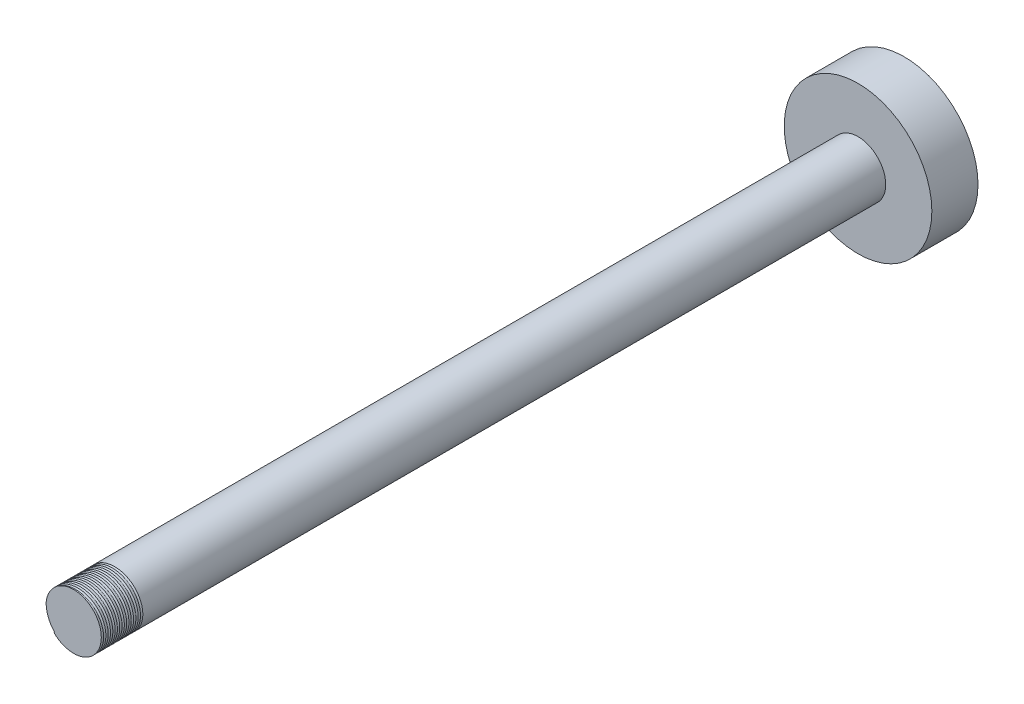
SolidWorks part; units mm, degrees
ref_plane "Front Plane" through (0, 0, 0) normal (0, 0, 1) x (1, 0, 0)
ref_plane "Top Plane" through (0, 0, 0) normal (0, 1, 0) x (1, 0, 0)
ref_plane "Right Plane" through (0, 0, 0) normal (1, 0, 0) x (0, 0, -1)
sketch "Sketch1" plane through (0, 0, 0) normal (0, 0, 1) x (1, 0, 0)
  circle A0 centre (0, 0) radius 16
  dimension "D1" = 32
extrude "Boss-Extrude1" add sketch "Sketch1" along normal blind 10
sketch "Sketch2" plane through (0, 0, 10) normal (0, 0, 1) x (1, 0, 0)
  circle A0 centre (0, 0) radius 6
  dimension "D1" = 12
extrude "Boss-Extrude2" add sketch "Sketch2" along normal blind 170
ref_plane "Plane1" through (0, 0, 0) normal (0, 1, 0) x (1, 0, 0)
sketch "Sketch7" plane through (0, 0, 180) normal (0, 0, 1) x (1, 0, 0)
  circle A0 centre (0, 0) radius 8
  dimension "D1" = 16
curve "Helix/Spiral1" pitch 1 height 9 turns 9
ref_plane "Plane2" through (0, 0, 0) normal (0, 0, 1) x (1, 0, 0)
sketch "Sketch8" plane through (0, 0, 0) normal (0, 1, 0) x (1, 0, 0)
  line L0 (-6, -10) -> (-6, -180) construction
  circle A0 centre (-6, -179.76) radius 0.25
  spline S0 degree 3 poles (-5.6569, -180) (-6.3926, -179.9793) (-7.5856, -179.9374) (-8.2077, -179.875) (-7.5836, -179.8125) (-5.8041, -179.75) (-3.1412, -179.6875) (0, -179.625) (3.1412, -179.5625) (5.8041, -179.5) (7.5835, -179.4375) (8.2083, -179.375) (7.5835, -179.3125) (5.8041, -179.25) (3.1412, -179.1875) (0, -179.125) (-3.1412, -179.0625) (-5.8041, -179) (-7.5835, -178.9375) (-8.2083, -178.875) (-7.5835, -178.8125) (-5.8041, -178.75) (-3.1412, -178.6875) (0, -178.625) (3.1412, -178.5625) (5.8041, -178.5) (7.5835, -178.4375) (8.2083, -178.375) (7.5835, -178.3125) (5.8041, -178.25) (3.1412, -178.1875) (0, -178.125) (-3.1412, -178.0625) (-5.8041, -178) (-7.5835, -177.9375) (-8.2083, -177.875) (-7.5835, -177.8125) (-5.8041, -177.75) (-3.1412, -177.6875) (0, -177.625) (3.1412, -177.5625) (5.8041, -177.5) (7.5835, -177.4375) (8.2083, -177.375) (7.5835, -177.3125) (5.8041, -177.25) (3.1412, -177.1875) (0, -177.125) (-3.1412, -177.0625) (-5.8041, -177) (-7.5835, -176.9375) (-8.2083, -176.875) (-7.5835, -176.8125) (-5.8041, -176.75) (-3.1412, -176.6875) (0, -176.625) (3.1412, -176.5625) (5.8041, -176.5) (7.5835, -176.4375) (8.2083, -176.375) (7.5835, -176.3125) (5.8041, -176.25) (3.1412, -176.1875) (0, -176.125) (-3.1412, -176.0625) (-5.8041, -176) (-7.5835, -175.9375) (-8.2083, -175.875) (-7.5835, -175.8125) (-5.8041, -175.75) (-3.1412, -175.6875) (0, -175.625) (3.1412, -175.5625) (5.8041, -175.5) (7.5835, -175.4375) (8.2083, -175.375) (7.5835, -175.3125) (5.8041, -175.25) (3.1412, -175.1875) (0, -175.125) (-3.1412, -175.0625) (-5.8041, -175) (-7.5835, -174.9375) (-8.2083, -174.875) (-7.5835, -174.8125) (-5.8041, -174.75) (-3.1412, -174.6875) (0, -174.625) (3.1412, -174.5625) (5.8041, -174.5) (7.5835, -174.4375) (8.2083, -174.375) (7.5835, -174.3125) (5.8041, -174.25) (3.1412, -174.1875) (0, -174.125) (-3.1412, -174.0625) (-5.8041, -174) (-7.5835, -173.9375) (-8.2083, -173.875) (-7.5835, -173.8125) (-5.8041, -173.75) (-3.1412, -173.6875) (0, -173.625) (3.1412, -173.5625) (5.8041, -173.5) (7.5835, -173.4375) (8.2083, -173.375) (7.5835, -173.3125) (5.8041, -173.25) (3.1412, -173.1875) (0, -173.125) (-3.1412, -173.0625) (-5.8041, -173) (-7.5835, -172.9375) (-8.2083, -172.875) (-7.5835, -172.8125) (-5.8041, -172.75) (-3.1412, -172.6875) (0, -172.625) (3.1412, -172.5625) (5.8041, -172.5) (7.5835, -172.4375) (8.2083, -172.375) (7.5835, -172.3125) (5.8041, -172.25) (3.1412, -172.1875) (0, -172.125) (-3.1412, -172.0625) (-5.8041, -172) (-7.5835, -171.9375) (-8.2083, -171.875) (-7.5835, -171.8125) (-5.8041, -171.75) (-3.1412, -171.6875) (0, -171.625) (3.1412, -171.5625) (5.8041, -171.5) (7.5835, -171.4375) (8.2083, -171.375) (7.5835, -171.3125) (5.8041, -171.25) (3.1413, -171.1875) (-0.0006, -171.125) (-3.139, -171.0626) (-4.9211, -171.0207) (-5.6569, -171) knots 0 0 0 0 0.006944 0.013889 0.020833 0.027778 0.034722 0.041667 0.048611 0.055556 0.0625 0.069444 0.076389 0.083333 0.090278 0.097222 0.104167 0.111111 0.118056 0.125 0.131944 0.138889 0.145833 0.152778 0.159722 0.166667 0.173611 0.180556 0.1875 0.194444 0.201389 0.208333 0.215278 0.222222 0.229167 0.236111 0.243056 0.25 0.256944 0.263889 0.270833 0.277778 0.284722 0.291667 0.298611 0.305556 0.3125 0.319444 0.326389 0.333333 0.340278 0.347222 0.354167 0.361111 0.368056 0.375 0.381944 0.388889 0.395833 0.402778 0.409722 0.416667 0.423611 0.430556 0.4375 0.444444 0.451389 0.458333 0.465278 0.472222 0.479167 0.486111 0.493056 0.5 0.506944 0.513889 0.520833 0.527778 0.534722 0.541667 0.548611 0.555556 0.5625 0.569444 0.576389 0.583333 0.590278 0.597222 0.604167 0.611111 0.618056 0.625 0.631944 0.638889 0.645833 0.652778 0.659722 0.666667 0.673611 0.680556 0.6875 0.694444 0.701389 0.708333 0.715278 0.722222 0.729167 0.736111 0.743056 0.75 0.756944 0.763889 0.770833 0.777778 0.784722 0.791667 0.798611 0.805556 0.8125 0.819444 0.826389 0.833333 0.840278 0.847222 0.854167 0.861111 0.868056 0.875 0.881944 0.888889 0.895833 0.902778 0.909722 0.916667 0.923611 0.930556 0.9375 0.944444 0.951389 0.958333 0.965278 0.972222 0.979167 0.986111 0.993056 1 1 1 1 construction
  dimension "D1" = 0.5
sweep "Cut-Sweep2" cut profiles "Sketch8" path "Helix/Spiral1"
